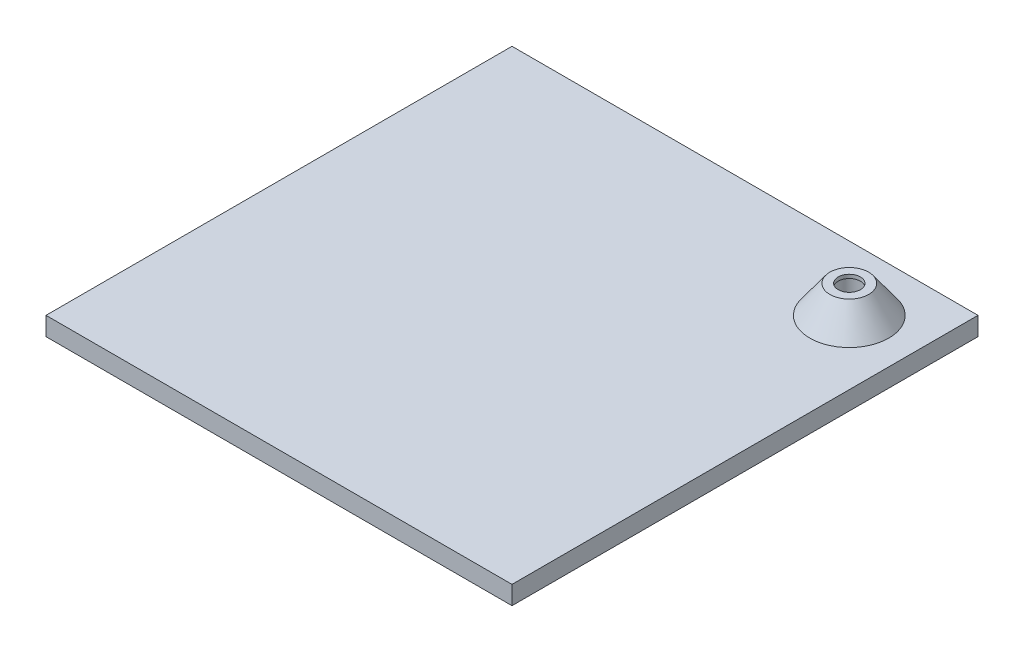
SolidWorks part; units mm, degrees
ref_plane "Front Plane" through (0, 0, 0) normal (0, 0, 1) x (1, 0, 0)
ref_plane "Top Plane" through (0, 0, 0) normal (0, 1, 0) x (1, 0, 0)
ref_plane "Right Plane" through (0, 0, 0) normal (1, 0, 0) x (0, 0, -1)
sketch "Sketch1" plane through (0, 0, 0) normal (0, 1, 0) x (1, 0, 0)
  line L1 (0, 0) -> (126, 0)
  line L2 (0, 0) -> (0, 126)
  line L3 (0, 126) -> (126, 126)
  line L4 (126, 0) -> (126, 126)
  dimension "D1" = 126
  dimension "D2" = 126
extrude "Boss-Extrude1" add sketch "Sketch1" along normal blind 5
sketch "Sketch3" plane through (0, 5, 0) normal (0, 1, 0) x (1, 0, 0)
  line L0 (108.6, 121.1) -> (108.6, 96.1) construction
  circle A0 centre (108.6, 108.6) radius 12.5
extrude "Boss-Extrude2" add sketch "Sketch3" along normal blind 7.5
sketch "Sketch4" plane through (0, 0, 0) normal (0, -1, 0) x (1, 0, 0)
  circle A1 centre (108.6, -108.6) radius 3.45
  dimension "D1" = 6.9
extrude "Cut-Extrude1" cut sketch "Sketch4" against normal blind 11.5
sketch "Sketch6" plane through (0, 12.5, 0) normal (0, 1, 0) x (1, 0, 0)
  line L0 (108.6, 121.1) -> (108.6, 96.1) construction
  circle A0 centre (108.6, 108.6) radius 12.5 construction
  circle A1 centre (108.6, 108.6) radius 3
  dimension "D1" = 6
extrude "Cut-Extrude2" cut sketch "Sketch6" against normal through all
chamfer "Chamfer1" distance 10 angle 36 1 edges at (108.6, 12.5, -96.1) first distance on face at (108.6, 12.5, -96.1)
